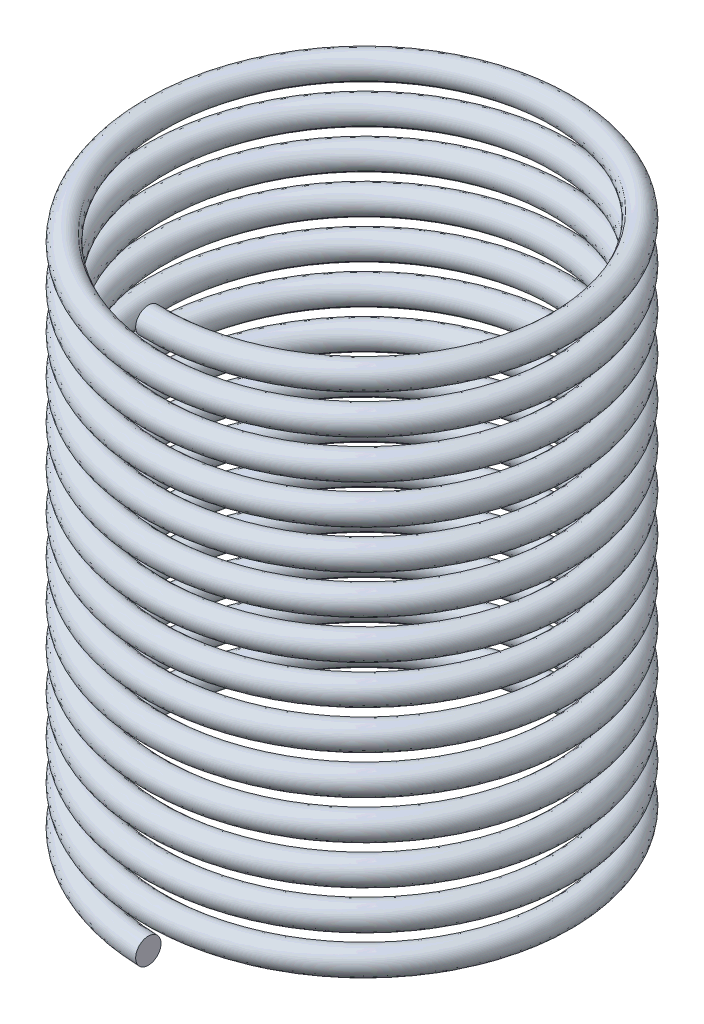
SolidWorks part; units mm, degrees
note: '?' marks a value the reader was unsure of.
material "Cast Stainless Steel"
ref_plane "Front Plane" through (0, 0, 0) normal (0, 0, 1) x (1, 0, 0)
ref_plane "Top Plane" through (0, 0, 0) normal (0, 1, 0) x (1, 0, 0)
ref_plane "Right Plane" through (0, 0, 0) normal (1, 0, 0) x (0, 0, -1)
sketch "Sketch1" plane through (0, 0, 0) normal (0, 1, 0) x (1, 0, 0)
  circle A0 centre (0, 0) radius 10.4375
  dimension "D1" = 20.875
curve "Helix/Spiral1" pitch 2 height 28 turns 14
sketch "Sketch2" plane through (0, 0, 0) normal (1, 0, 0) x (0, 0, -1)
  circle A0 centre (-10.4375, 0) radius 0.65
  spline S0 degree 3 poles (-10.4375, 0) (-10.4375, 0.0414) (-9.894, 0.1251) (-7.5726, 0.25) (-4.0982, 0.375) (0, 0.5) (4.0982, 0.625) (7.5726, 0.75) (9.894, 0.875) (10.7092, 1) (9.894, 1.125) (7.5726, 1.25) (2.9401, 1.4167) (-2.9401, 1.5833) (-7.5726, 1.75) (-9.894, 1.875) (-10.7092, 2) (-9.894, 2.125) (-7.5726, 2.25) (-2.9401, 2.4167) (2.9401, 2.5833) (7.5726, 2.75) (9.894, 2.875) (10.7092, 3) (9.894, 3.125) (7.5726, 3.25) (2.9401, 3.4167) (-2.9401, 3.5833) (-7.5726, 3.75) (-9.894, 3.875) (-10.7092, 4) (-9.894, 4.125) (-7.5726, 4.25) (-2.9401, 4.4167) (2.9401, 4.5833) (7.5726, 4.75) (9.894, 4.875) (10.7092, 5) (9.894, 5.125) (7.5726, 5.25) (2.9401, 5.4167) (-2.9401, 5.5833) (-7.5726, 5.75) (-9.894, 5.875) (-10.7092, 6) (-9.894, 6.125) (-7.5726, 6.25) (-2.9401, 6.4167) (2.9401, 6.5833) (7.5726, 6.75) (9.894, 6.875) (10.7092, 7) (9.894, 7.125) (7.5726, 7.25) (2.9401, 7.4167) (-2.9401, 7.5833) (-7.5726, 7.75) (-9.894, 7.875) (-10.7092, 8) (-9.894, 8.125) (-7.5726, 8.25) (-2.9401, 8.4167) (2.9401, 8.5833) (7.5726, 8.75) (9.894, 8.875) (10.7092, 9) (9.894, 9.125) (7.5726, 9.25) (2.9401, 9.4167) (-2.9401, 9.5833) (-7.5726, 9.75) (-9.894, 9.875) (-10.7092, 10) (-9.894, 10.125) (-7.5726, 10.25) (-2.9401, 10.4167) (2.9401, 10.5833) (7.5726, 10.75) (9.894, 10.875) (10.7092, 11) (9.894, 11.125) (7.5726, 11.25) (2.9401, 11.4167) (-2.9401, 11.5833) (-7.5726, 11.75) (-9.894, 11.875) (-10.7092, 12) (-9.894, 12.125) (-7.5726, 12.25) (-2.9401, 12.4167) (2.9401, 12.5833) (7.5726, 12.75) (9.894, 12.875) (10.7092, 13) (9.894, 13.125) (7.5726, 13.25) (2.9401, 13.4167) (-2.9401, 13.5833) (-7.5726, 13.75) (-9.894, 13.875) (-10.7092, 14) (-9.894, 14.125) (-7.5726, 14.25) (-2.9401, 14.4167) (2.9401, 14.5833) (7.5726, 14.75) (9.894, 14.875) (10.7092, 15) (9.894, 15.125) (7.5726, 15.25) (2.9401, 15.4167) (-2.9401, 15.5833) (-7.5726, 15.75) (-9.894, 15.875) (-10.7092, 16) (-9.894, 16.125) (-7.5726, 16.25) (-2.9401, 16.4167) (2.9401, 16.5833) (7.5726, 16.75) (9.894, 16.875) (10.7092, 17) (9.894, 17.125) (7.5726, 17.25) (2.9401, 17.4167) (-2.9401, 17.5833) (-7.5726, 17.75) (-9.894, 17.875) (-10.7092, 18) (-9.894, 18.125) (-7.5726, 18.25) (-2.9401, 18.4167) (2.9401, 18.5833) (7.5726, 18.75) (9.894, 18.875) (10.7092, 19) (9.894, 19.125) (7.5726, 19.25) (2.9401, 19.4167) (-2.9401, 19.5833) (-7.5726, 19.75) (-9.894, 19.875) (-10.7092, 20) (-9.894, 20.125) (-7.5726, 20.25) (-2.9401, 20.4167) (2.9401, 20.5833) (7.5726, 20.75) (9.894, 20.875) (10.7092, 21) (9.894, 21.125) (7.5726, 21.25) (2.9401, 21.4167) (-2.9401, 21.5833) (-7.5726, 21.75) (-9.894, 21.875) (-10.7092, 22) (-9.894, 22.125) (-7.5726, 22.25) (-2.9401, 22.4167) (2.9401, 22.5833) (7.5726, 22.75) (9.894, 22.875) (10.7092, 23) (9.894, 23.125) (7.5726, 23.25) (2.9401, 23.4167) (-2.9401, 23.5833) (-7.5726, 23.75) (-9.894, 23.875) (-10.7092, 24) (-9.894, 24.125) (-7.5726, 24.25) (-2.9401, 24.4167) (2.9401, 24.5833) (7.5726, 24.75) (9.894, 24.875) (10.7092, 25) (9.894, 25.125) (7.5726, 25.25) (2.9401, 25.4167) (-2.9401, 25.5833) (-7.5726, 25.75) (-9.894, 25.875) (-10.7092, 26) (-9.894, 26.125) (-7.5726, 26.25) (-2.9401, 26.4167) (2.9401, 26.5833) (7.5726, 26.75) (9.894, 26.875) (10.7092, 27) (9.894, 27.125) (7.5726, 27.25) (4.0982, 27.375) (0, 27.5) (-4.0982, 27.625) (-7.5726, 27.75) (-9.894, 27.8749) (-10.4375, 27.9586) (-10.4375, 28) knots 0 0 0 0 0.004464 0.008929 0.013393 0.017857 0.022321 0.026786 0.03125 0.035714 0.040179 0.044643 0.049107 0.058036 0.0625 0.066964 0.071429 0.075893 0.080357 0.084821 0.09375 0.098214 0.102679 0.107143 0.111607 0.116071 0.120536 0.129464 0.133929 0.138393 0.142857 0.147321 0.151786 0.15625 0.165179 0.169643 0.174107 0.178571 0.183036 0.1875 0.191964 0.200893 0.205357 0.209821 0.214286 0.21875 0.223214 0.227679 0.236607 0.241071 0.245536 0.25 0.254464 0.258929 0.263393 0.272321 0.276786 0.28125 0.285714 0.290179 0.294643 0.299107 0.308036 0.3125 0.316964 0.321429 0.325893 0.330357 0.334821 0.34375 0.348214 0.352679 0.357143 0.361607 0.366071 0.370536 0.379464 0.383929 0.388393 0.392857 0.397321 0.401786 0.40625 0.415179 0.419643 0.424107 0.428571 0.433036 0.4375 0.441964 0.450893 0.455357 0.459821 0.464286 0.46875 0.473214 0.477679 0.486607 0.491071 0.495536 0.5 0.504464 0.508929 0.513393 0.522321 0.526786 0.53125 0.535714 0.540179 0.544643 0.549107 0.558036 0.5625 0.566964 0.571429 0.575893 0.580357 0.584821 0.59375 0.598214 0.602679 0.607143 0.611607 0.616071 0.620536 0.629464 0.633929 0.638393 0.642857 0.647321 0.651786 0.65625 0.665179 0.669643 0.674107 0.678571 0.683036 0.6875 0.691964 0.700893 0.705357 0.709821 0.714286 0.71875 0.723214 0.727679 0.736607 0.741071 0.745536 0.75 0.754464 0.758929 0.763393 0.772321 0.776786 0.78125 0.785714 0.790179 0.794643 0.799107 0.808036 0.8125 0.816964 0.821429 0.825893 0.830357 0.834821 0.84375 0.848214 0.852679 0.857143 0.861607 0.866071 0.870536 0.879464 0.883929 0.888393 0.892857 0.897321 0.901786 0.90625 0.915179 0.919643 0.924107 0.928571 0.933036 0.9375 0.941964 0.950893 0.955357 0.959821 0.964286 0.96875 0.973214 0.977679 0.982143 0.986607 0.991071 0.995536 1 1 1 1 construction
  dimension "D1" = 1.3
sweep "Sweep1" add profiles "Sketch2" path "Helix/Spiral1"
ref_plane "Bottom Face" through (0, 0, 0) normal (0, 1, 0) x (1, 0, 0)
ref_plane "Top Face" through (0, 28.65, 0) normal (0, 1, 0) x (1, 0, 0)
ref_axis "Axis1" through (0, -2.83, 0) along (0, 1, 0)?
equation "\"innerDiameter\"= 5in / 8"
equation "\"springLength\"= 28mm"
equation "\"D1@Sketch1\"=\"innerDiameter\" + 5"
